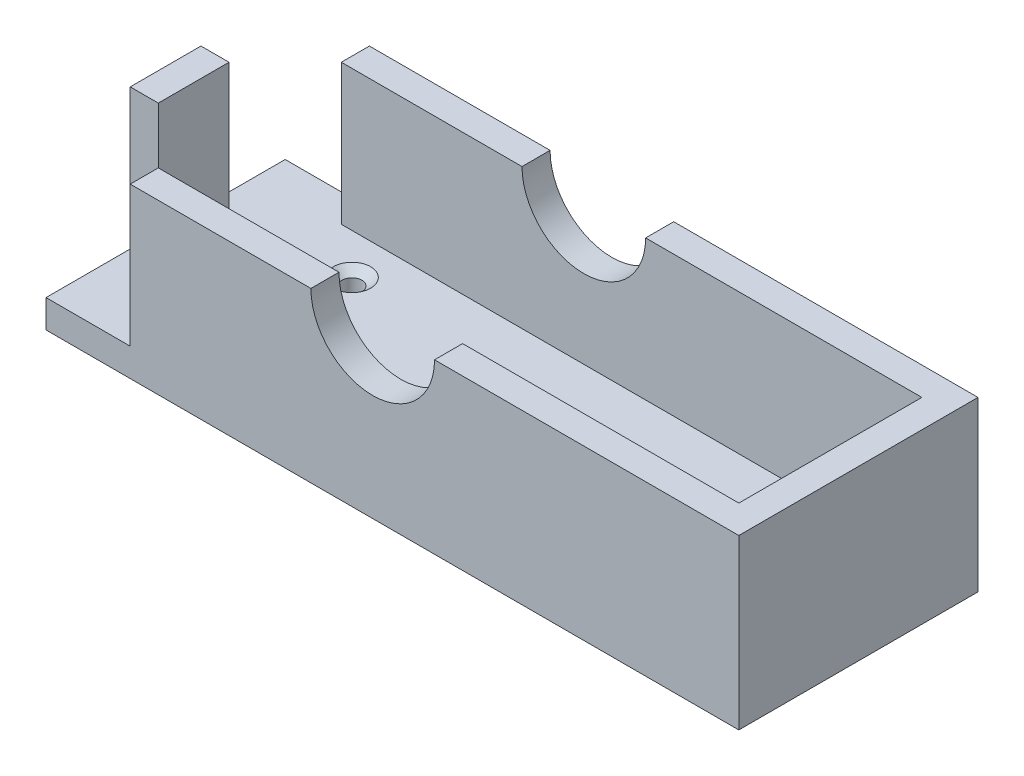
SolidWorks part; units mm, degrees
material "PET"
ref_plane "Front Plane" through (0, 0, 0) normal (0, 0, 1) x (1, 0, 0)
ref_plane "Top Plane" through (0, 0, 0) normal (0, 1, 0) x (1, 0, 0)
ref_plane "Right Plane" through (0, 0, 0) normal (1, 0, 0) x (0, 0, -1)
sketch "Sketch1" plane through (0, 0, 0) normal (0, 1, 0) x (1, 0, 0)
  line L5 (-69.4555, 10.1298) -> (74.5625, 10.1298)
  line L6 (-69.4555, 10.1298) -> (-69.4555, -31.2722)
  line L7 (-69.4555, -31.2722) -> (74.5625, -31.2722)
  line L8 (74.5625, 10.1298) -> (74.5625, -31.2722)
  line L9 (-75.8055, 16.4798) -> (80.9125, 16.4798)
  line L10 (-75.8055, 16.4798) -> (-75.8055, -37.6222)
  line L11 (-75.8055, -37.6222) -> (80.9125, -37.6222)
  line L12 (80.9125, 16.4798) -> (80.9125, -37.6222)
  line L14 (74.5625, 10.1298) -> (74.5625, 16.4798)
  line L15 (74.5625, -31.2722) -> (74.5625, -37.6222)
  line L16 (-56.7555, -31.2722) -> (-56.7555, -37.6222)
  line L17 (-75.8055, -18.5722) -> (-69.4555, -18.5722)
  line L18 (-69.4555, -31.2722) -> (-56.7555, -31.2722)
  line L19 (-75.8055, -31.2722) -> (-75.8055, -37.6222)
  line L20 (-75.8055, -37.6222) -> (-56.7555, -37.6222)
  line L21 (-56.7555, -31.2722) -> (-56.7555, -37.6222)
  line L22 (-75.8055, -18.5722) -> (-69.4555, -18.5722)
  line L23 (-75.8055, -18.5722) -> (-75.8055, -31.2722)
  line L25 (-69.4555, -18.5722) -> (-69.4555, -31.2722)
  line L26 (-75.8055, 16.4798) -> (-56.7555, 16.4798)
  line L27 (-75.8055, 16.4798) -> (-75.8055, 10.1298)
  line L28 (-69.4555, 10.1298) -> (-56.7555, 10.1298)
  line L29 (-56.7555, 16.4798) -> (-56.7555, 10.1298)
  line L30 (-75.8055, 16.4798) -> (-69.4555, 16.4798)
  line L31 (-75.8055, 16.4798) -> (-75.8055, -2.5702)
  line L32 (-75.8055, -2.5702) -> (-69.4555, -2.5702)
  line L33 (-69.4555, 10.1298) -> (-69.4555, -2.5702)
  point P0 (-49.1267, -9.4869)
  point P1 (-49.1267, 8.7015)
  point P2 (50.9319, 8.7015)
  point P3 (50.9319, -9.4869)
  point P8 (0, 0)
  dimension "D1" = 156.718
  dimension "D2" = 54.102
  dimension "D3" = 144.018
  dimension "D4" = 41.402
  dimension "D5" = 6.35
  dimension "D6" = 19.05
  dimension "D7" = 19.05
  dimension "D8" = 19.05
sketch "Sketch3" plane through (0, 0, 0) normal (0, 1, 0) x (1, 0, 0)
  line L1 (-69.4555, 10.1298) -> (74.5625, 10.1298)
  line L2 (-69.4555, 10.1298) -> (-69.4555, -31.2722)
  line L3 (-69.4555, -31.2722) -> (74.5625, -31.2722)
  line L4 (74.5625, 10.1298) -> (74.5625, -31.2722)
ref_plane "Plane2" through (72.39, 0, 0) normal (1, 0, 0) x (0, 0, -1)
extrude "Boss-Extrude1" add sketch "Sketch1" along normal blind 38.1 contours L8 L15 L11 L12 L9 L14 | L32 L10 L17 L6 region at (-72.6305, 0, 10.5712) region at (77.7375, 0, 10.5712)
extrude "Boss-Extrude2" add sketch "Sketch1<4>" along normal blind 6.35 contours L8 L5 L6 L7 | L6 L5 L8 L7 region at (2.5535, 0, 10.5712)
sketch "Sketch1<4>" plane through (0, 0, 0) normal (0, 1, 0) x (1, 0, 0) same geometry as "Sketch1"
extrude "Boss-Extrude3" add sketch "Sketch1<5>" along normal blind 38.1 contours L5 L14 L9 | L15 L7 L11 region at (8.9035, 0, -13.3048) region at (8.9035, 0, 34.4472)
sketch "Sketch1<5>" plane through (0, 0, 0) normal (0, 1, 0) x (1, 0, 0) same geometry as "Sketch1"
sketch "Sketch7" plane through (0, 6.35, 0) normal (0, 1, 0) x (1, 0, 0)
  line L4 (-69.4555, -2.5702) -> (-69.4555, -18.5722) construction
  line L5 (-56.7555, 16.4798) -> (80.9125, 16.4798) construction
  point P0 (-45.135, 0.9223)
  point P1 (-45.135, -21.9377)
  point P2 (50.115, -22.0012)
  point P3 (50.115, 0.8588)
  dimension "D1" = 22.86
  dimension "D2" = 22.86
  dimension "D3" = 95.25
  dimension "D4" = 95.25
  dimension "D5" = 24.3205
  dimension "D7" = 15.621
hole_wizard "CSK for #8 Flat Head Machine Screw (100)2" positions "Sketch8" profile "Sketch9" countersink size "#8" standard "ANSI Inch" end condition through all
sketch "Sketch8" plane through (0, 6.35, 0) normal (0, 1, 0) x (1, 0, 0)
  point P0 (-45.135, -21.9377)
  point P3 (-45.135, 0.9223)
  point P6 (50.115, 0.8588)
  point P9 (50.115, -22.0012)
sketch "Sketch9" plane through (-45.135, 6.35, 21.9377) normal (1, 0, 0) x (0, 0, 1)
  line L0 (0, 0) -> (0, 6.35)
  line L1 (0, 6.35) -> (2.2479, 6.35)
  line L2 (2.2479, 6.35) -> (2.2479, 1.6518)
  line L3 (2.2479, 1.6518) -> (4.2164, 0)
  line L5 (4.2164, 0) -> (0, 0)
  line L6 (-2.2479, 1.6518) -> (-4.2164, 0) construction
  line L11 (0, -6.35) -> (0, 107.95) construction
  dimension "Thru Hole Dia." = 4.4958
  dimension "Thru Hole Depth" = 6.35
  dimension "Near C'Sink Dia." = 8.4328
  dimension "Near C'Sink Angle" = 100
extrude "Boss-Extrude6" add sketch "Sketch1<8>" along normal blind 6.35 contours L17 L10 L11 L16 L7 L6 region at (-69.7249, 0, 24.9222)
sketch "Sketch1<8>" plane through (0, 0, 0) normal (0, 1, 0) x (1, 0, 0) same geometry as "Sketch1"
sketch "Sketch11" plane through (0, 0, 37.6222) normal (0, 0, 1) x (1, 0, 0)
  line L0 (-56.7555, 38.1) -> (80.9125, 38.1) construction
  arc A0 (-15.8864, 38.1) -> (12.0785, 38.1) centre (-1.9039, 38.1) ccw
  point P0 (-15.8864, 38.1)
  point P1 (12.0785, 38.1)
extrude "Cut-Extrude3" cut sketch "Sketch11" against normal through all and the other way through all
extrude "Boss-Extrude7" add sketch "Sketch1<9>" along normal blind 6.35 contours L10 L32 L6 L5 L29 L26 L9 region at (-69.7249, 0, -3.7798)
sketch "Sketch1<9>" plane through (0, 0, 0) normal (0, 1, 0) x (1, 0, 0) same geometry as "Sketch1"
